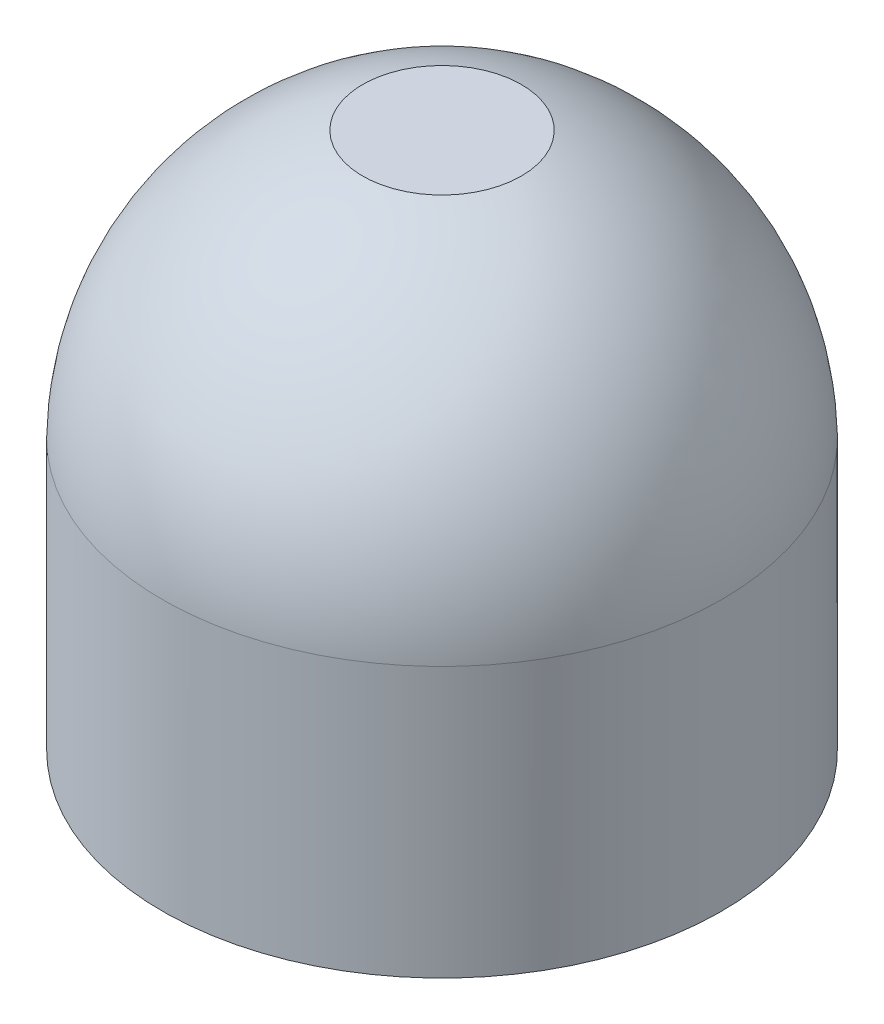
SolidWorks part; units mm, degrees
ref_plane "Front Plane" through (0, 0, 0) normal (0, 0, 1) x (1, 0, 0)
ref_plane "Top Plane" through (0, 0, 0) normal (0, 1, 0) x (1, 0, 0)
ref_plane "Right Plane" through (0, 0, 0) normal (1, 0, 0) x (0, 0, -1)
sketch "Sketch1" plane through (0, 0, 0) normal (0, 1, 0) x (1, 0, 0)
  circle A0 centre (0, 0) radius 5.18
  circle A1 centre (0, 0) radius 4.38
extrude "Boss-Extrude1" add sketch "Sketch1" along normal blind 5
sketch "Sketch2" plane through (0, 0, 0) normal (0, 1, 0) x (1, 0, 0)
  line L1 (1.3277, 3.7956) -> (1.3277, 5.7011)
  line L2 (1.3277, 5.7011) -> (-1.5, 5.7011)
  line L3 (-1.5, 5.7011) -> (-1.5, 3.7011)
  line L4 (-1.5, 3.7011) -> (1.3277, 3.7956)
extrude "Cut-Extrude1" cut sketch "Sketch2" along normal blind 5
sketch "Sketch4" plane through (0, 0, 0) normal (0, 0, 1) x (1, 0, 0)
  line L0 (5.18, 5) -> (0, 5)
  line L1 (0, 5) -> (0, 10.18)
  arc A0 (0, 10.18) -> (5.18, 5) centre (-0.1089, 4.8911) cw
  dimension "D1" = 5.18
  dimension "D2" = 5.18
revolve "Revolve1" add sketch "Sketch4" angle 360 about L1
ref_plane "Plane1" through (0, 5, 0) normal (0, -1, 0) x (-1, 0, 0)
sketch "Sketch5" plane through (0, 5, 0) normal (0, -1, 0) x (-1, 0, 0)
  line L2 (1.5, 3.4369) -> (1.5, 6)
  line L3 (1.5, 6) -> (-1.3277, 6)
  line L4 (-1.3277, 3.5071) -> (-1.3277, 6)
  arc A0 (-1.3277, 3.5071) -> (1.5, 3.4369) centre (0, 0) ccw
extrude "Cut-Extrude2" cut sketch "Sketch5" against normal blind 2
ref_plane "Plane2" through (0, 10.29, 0) normal (0, -1, 0) x (-1, 0, 0)
sketch "Sketch6" plane through (0, 10.29, 0) normal (0, -1, 0) x (-1, 0, 0)
  circle A0 centre (0, 0) radius 2
extrude "Cut-Extrude4" cut sketch "Sketch6" along normal blind 0.35
